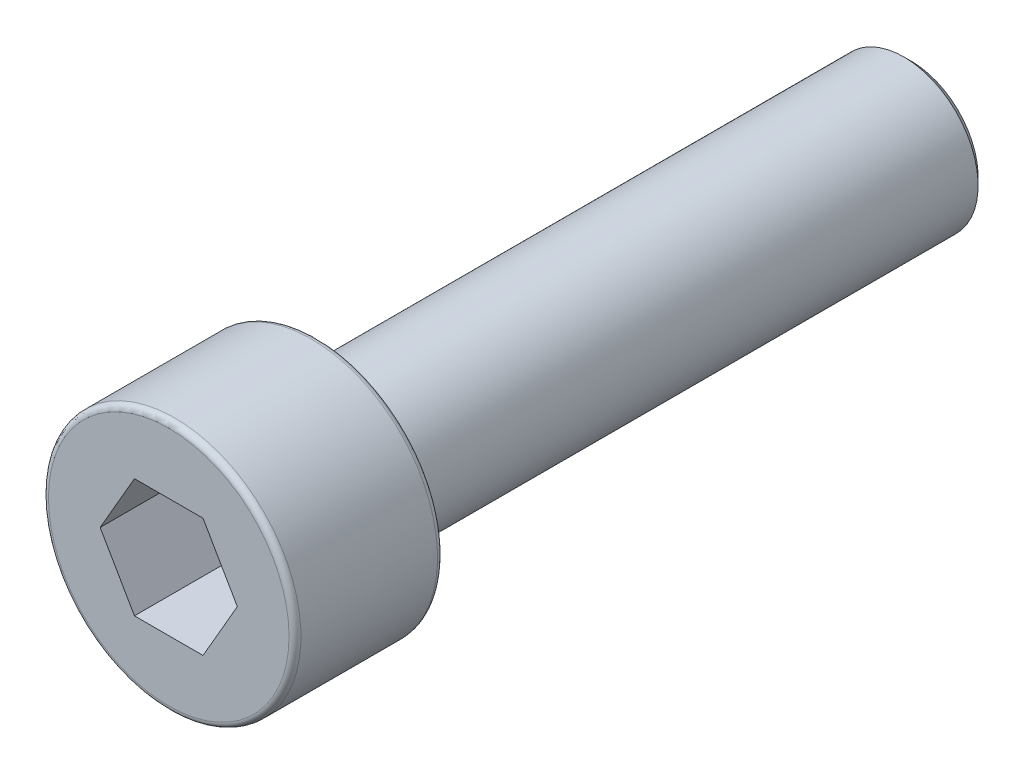
SolidWorks part; units mm, degrees
ref_plane "Front Plane" through (0, 0, 0) normal (0, 0, 1) x (1, 0, 0)
ref_plane "Top Plane" through (0, 0, 0) normal (0, 1, 0) x (1, 0, 0)
ref_plane "Right Plane" through (0, 0, 0) normal (1, 0, 0) x (0, 0, -1)
ref_plane "Plane1" through (0, 0, 25) normal (0, 0, 1) x (1, 0, 0)
sketch "Sketch1" plane through (0, 0, 25) normal (0, 0, 1) x (1, 0, 0)
  circle A0 centre (0, 0) radius 4.25
extrude "Boss-Extrude1" add sketch "Sketch1" against normal blind 5
sketch "Sketch2" plane through (0, 0, 20) normal (0, 0, -1) x (-1, 0, 0)
  circle A0 centre (0, 0) radius 2.5
extrude "Boss-Extrude2" add sketch "Sketch2" along normal blind 20
sketch "Sketch3" plane through (0, 0, 25) normal (0, 0, 1) x (1, 0, 0)
  line L0 (-2.3094, 0) -> (-1.1547, -2)
  line L1 (-1.1547, -2) -> (1.1547, -2)
  line L2 (1.1547, -2) -> (2.3094, 0)
  line L3 (2.3094, 0) -> (1.1547, 2)
  line L4 (1.1547, 2) -> (-1.1547, 2)
  line L5 (-1.1547, 2) -> (-2.3094, 0)
extrude "Cut-Extrude1" cut sketch "Sketch3" against normal blind 4
chamfer "Chamfer1" distance 0.25 angle 45 1 edges at (-2.5, 0, 0)
fillet "Fillet1" radius 0.2 2 edges at (-4.25, 0, 20) (-4.25, 0, 25) tangent propagation no
ref_axis "Axis1" through (0, 0, -2.6747) along (0, 0, 1)
